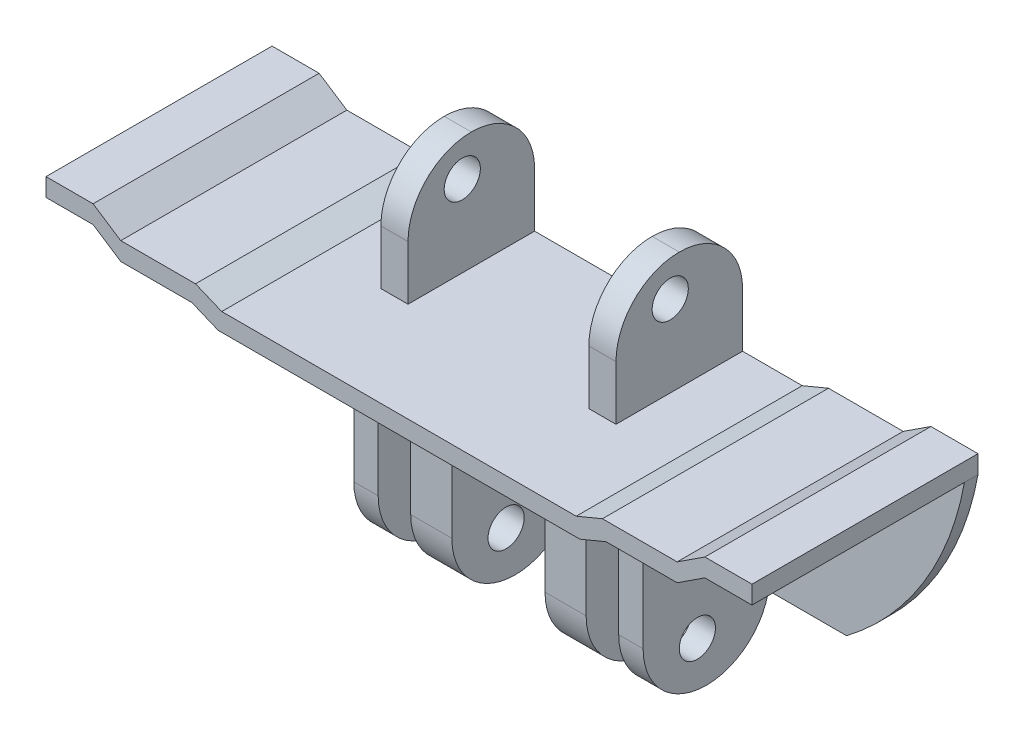
SolidWorks part; units mm, degrees
ref_plane "Front Plane" through (0, 0, 0) normal (0, 0, 1) x (1, 0, 0)
ref_plane "Top Plane" through (0, 0, 0) normal (0, 1, 0) x (1, 0, 0)
ref_plane "Right Plane" through (0, 0, 0) normal (1, 0, 0) x (0, 0, -1)
sketch "Sketch2" plane through (0, 0, 0) normal (0, 0, 1) x (1, 0, 0)
  line L0 (-5, 6) -> (-10, 6)
  line L1 (-5, 6) -> (5, 6) construction
  line L2 (-5, 6) -> (-5, -19) construction
  line L4 (5, 6) -> (5, -19) construction
  line L7 (-10, 6) -> (-10, -19)
  line L8 (-10, -19) -> (-5, -19)
  line L9 (-5, -19) -> (-5, 6)
  line L10 (0, 6) -> (0, -6) construction
  line L11 (10, -19) -> (5, -19)
  line L12 (10, 6) -> (10, -19)
  line L13 (5, 6) -> (10, 6)
  line L14 (5, -19) -> (5, 6)
  point P0 (0, 0)
  point P11 (0, 0)
  point P16 (0, 6)
  dimension "D1" = 25
  dimension "D2" = 10
  dimension "D3" = 5
extrude "Boss-Extrude1" add sketch "Sketch2" along normal blind 14
sketch "Sketch4" plane through (0, 0, 0) normal (0, 0, 1) x (1, 0, 0)
  line L0 (0, 0) -> (0, 50000) construction
  line L1 (-6.1796, 6) -> (49993.8204, 6) construction
  line L2 (-10, 6) -> (-20, 6)
  line L3 (10, 6) -> (20, 6)
  line L4 (-20, 6) -> (-22.9016, 7.2064)
  line L5 (-22.9016, 7.2064) -> (-26, 7.2064)
  line L6 (-10, 8) -> (-19.6008, 8)
  line L7 (-19.6008, 8) -> (-22.5024, 9.2064)
  line L8 (-22.5024, 9.2064) -> (-26, 9.2064)
  line L9 (-26, 9.2064) -> (-26, 7.2064)
  line L10 (-10, 6) -> (10, 6)
  line L11 (-10, 8) -> (10, 8)
  line L12 (10, 8) -> (19.6008, 8)
  line L13 (19.6008, 8) -> (22.5024, 9.2064)
  line L14 (20, 6) -> (22.9016, 7.2064)
  line L15 (22.9016, 7.2064) -> (26, 7.2064)
  line L17 (22.5024, 9.2064) -> (26, 9.2064)
  line L18 (-26, 7.2064) -> (-30.766, 7.2064)
  line L19 (-30.766, 7.2064) -> (-33.8312, 9.2064)
  line L20 (-33.8312, 9.2064) -> (-39.0379, 9.2064)
  line L21 (-39.0379, 9.2064) -> (-39.0379, 11.2064)
  line L22 (-39.0379, 11.2064) -> (-33.8312, 11.2064)
  line L23 (-26, 9.2064) -> (-30.766, 9.2064)
  line L24 (-30.766, 9.2064) -> (-33.8312, 11.2064)
  line L25 (26, 7.2064) -> (30.766, 7.2064)
  line L26 (26, 9.2064) -> (30.766, 9.2064)
  line L27 (30.766, 9.2064) -> (33.8312, 11.2064)
  line L28 (30.766, 7.2064) -> (33.8312, 9.2064)
  line L29 (33.8312, 9.2064) -> (39.0379, 9.2064)
  line L30 (39.0379, 9.2064) -> (39.0379, 11.2064)
  line L31 (39.0379, 11.2064) -> (33.8312, 11.2064)
  line L32 (26, 7.2064) -> (26, 9.2064)
  point P19 (0, 6)
  point P20 (0, 8)
  dimension "D1" = 10
  dimension "D2" = 2
extrude "Boss-Extrude3" add sketch "Sketch4" along normal blind 25 contours L23 L24 L22 L21 L20 L19 L18 L9 | L15 L32 L17 L13 L12 L11 L6 L7 L8 L9 L5 L4 L2 L10 L3 L14 | L32 L25 L28 L29 L30 L31 L27 L26 region at (0, 7.2239, 0) region at (-32.5189, 9.2402, 0) region at (32.5189, 9.2402, 0)
sketch "Sketch9" plane through (0, 0, 14) normal (0, 0, 1) x (1, 0, 0)
  line L0 (-10, -19) -> (-5, -19) construction
  line L1 (-5, 6) -> (-7.5, 6)
  line L2 (-5, 6) -> (-5, -19)
  line L3 (-5, -19) -> (-7.5, -19)
  line L4 (-7.5, 6) -> (-7.5, -19)
  line L5 (0, 7.972) -> (0, -7.972) construction
  line L6 (5, -19) -> (7.5, -19)
  line L7 (7.5, 6) -> (7.5, -19)
  line L8 (5, 6) -> (7.5, 6)
  line L9 (5, 6) -> (5, -19)
  point P11 (0, 0)
  dimension "D1" = 2.5
extrude "Cut-Extrude1" [suppressed] cut sketch "Sketch9" against normal blind 10
sketch "Sketch5" plane through (0, 0, 0) normal (0, 0, 1) x (1, 0, 0)
  line L0 (-10, 4.6) -> (-10, 50004.6) construction
  line L1 (0, 0) -> (0, 50000) construction
  line L2 (-10, 8) -> (-10, 21)
  line L3 (-19.6008, 8) -> (19.6008, 8) construction
  line L4 (-10, 21) -> (-13, 21)
  line L5 (-13, 21) -> (-13, 8)
  line L6 (-13, 8) -> (-10, 8)
  line L7 (13, 8) -> (10, 8)
  line L8 (13, 21) -> (13, 8)
  line L9 (10, 21) -> (13, 21)
  line L10 (10, 8) -> (10, 21)
  dimension "D1" = 3
  dimension "D2" = 13
extrude "Boss-Extrude4" add sketch "Sketch5" along normal blind 14
sketch "Sketch7" plane through (0, 0, 0) normal (0, 0, 1) x (1, 0, 0)
  line L0 (-13, 5.6) -> (-13, -49994.4) construction
  line L1 (-19.6008, 5.6) -> (-19.6008, -49994.4) construction
  line L2 (-10.0004, -19) -> (49989.9996, -19) construction
  line L3 (-15.0004, 6) -> (-50015.0004, 6) construction
  line L4 (-16, 6) -> (-16, -19)
  line L5 (-16, -19) -> (-13, -19)
  line L6 (-13, -19) -> (-13, 6)
  line L7 (-13, 6) -> (-16, 6)
  line L8 (0, 0) -> (0, -50000) construction
  line L13 (0, -13.75) -> (0, 13.75) construction
  line L14 (13, -19) -> (13, 6)
  line L15 (16, -19) -> (13, -19)
  line L16 (16, 6) -> (16, -19)
  line L17 (13, 6) -> (16, 6)
  dimension "D1" = 3
extrude "Boss-Extrude5" add sketch "Sketch7" along normal blind 14
sketch "Sketch15" plane through (0, -19, 0) normal (0, -1, 0) x (1, 0, 0)
  line L16 (-10, 14) -> (-9.7, 14)
  line L17 (-10, 14) -> (-5, 14) construction
  line L18 (-10, 14) -> (-10, 0) construction
  line L19 (-9.7, 14) -> (-9.7, 0)
  line L20 (-10, 0) -> (-5, 0) construction
  line L21 (-9.7, 0) -> (-10, 0)
  line L22 (-10, 0) -> (-10, 14)
  line L23 (0, -13.75) -> (0, 13.75) construction
  line L24 (9.7, 0) -> (10, 0)
  line L25 (9.7, 14) -> (9.7, 0)
  line L26 (10, 14) -> (9.7, 14)
  line L27 (10, 0) -> (10, 14)
  line L28 (-13, 14) -> (-13.3, 14)
  line L29 (-16, 14) -> (-13, 14) construction
  line L30 (-13.3, 14) -> (-13.3, 0)
  line L31 (-16, 0) -> (-13, 0) construction
  line L32 (-13.3, 0) -> (-13, 0)
  line L33 (-13, 0) -> (-13, 14)
  line L34 (13.3, 0) -> (13, 0)
  line L35 (13.3, 14) -> (13.3, 0)
  line L36 (13, 14) -> (13.3, 14)
  line L37 (13, 0) -> (13, 14)
  dimension "D1" = 0.3
  dimension "D2" = 0.3
extrude "Cut-Extrude2" cut sketch "Sketch15" against normal up to surface (25 mm away) up to face at (0, 6, 8.1)
sketch "Sketch16" plane through (0, -19, 0) normal (0, -1, 0) x (1, 0, 0)
  line L0 (-5, 14) -> (-5.15, 14)
  line L1 (-9.7, 14) -> (-5, 14) construction
  line L2 (-5.15, 14) -> (-5.15, 0)
  line L3 (-9.7, 0) -> (-5, 0) construction
  line L4 (-5.15, 0) -> (-5, 0)
  line L5 (-5, 0) -> (-5, 14)
  line L6 (0, -13.75) -> (0, 13.75) construction
  line L7 (5.15, 0) -> (5, 0)
  line L8 (5.15, 14) -> (5.15, 0)
  line L9 (5, 14) -> (5.15, 14)
  line L10 (5, 0) -> (5, 14)
  dimension "D1" = 0.15
extrude "Cut-Extrude3" cut sketch "Sketch16" against normal up to surface (25 mm away) up to face at (0, 6, 8.1)
fillet "Fillet1" radius 7 8 edges at (7.425, -19, 0) (7.425, -19, 14) (-7.425, -19, 0) (-7.425, -19, 14) (-14.65, -19, 0) (-14.65, -19, 14) (14.65, -19, 0) (14.65, -19, 14)
hole_wizard "Ø4.0mm Dowel Hole2" positions "Sketch10" profile "Sketch11" hole size "Ø4.0" standard "ANSI Metric" end condition through all
sketch "Sketch10" plane through (16, 0, 0) normal (1, 0, 0) x (0, 0, -1)
  line L7 (-25, 6) -> (0, 6) construction
  line L9 (-14, -12) -> (-14, 6) construction
  point P0 (-8, -14)
  dimension "D1" = 6
  dimension "D2" = 20
sketch "Sketch11" plane through (16, -14, 8) normal (0, 1, 0) x (0, 0, -1)
  line L0 (0, 0) -> (0, 55.0379)
  line L1 (0, 55.0379) -> (2, 55.0379)
  line L2 (2, 55.0379) -> (2, 0)
  line L5 (2, 0) -> (0, 0)
  line L11 (0, -6.35) -> (0, 107.95) construction
  dimension "Thru Hole Dia." = 4
  dimension "Thru Hole Depth" = 55.0379
fillet "Fillet2" radius 7 4 edges at (-11.5, 21, 0) (-11.5, 21, 14) (11.5, 21, 0) (11.5, 21, 14)
hole_wizard "Ø4.0mm Dowel Hole1" positions "Sketch12" profile "Sketch13" hole size "Ø4.0" standard "ANSI Metric"
sketch "Sketch12" plane through (13, 0, 0) normal (1, 0, 0) x (0, 0, -1)
  line L1 (-25, 8) -> (0, 8) construction
  line L2 (-25, 8) -> (0, 8)
  circle A8 centre (-8, -14) radius 2 construction
  circle A9 centre (-8, -14) radius 2
  point P10 (-8, 17)
  dimension "D1" = 9
sketch "Sketch13" plane through (13, 17, 8) normal (0, 1, 0) x (0, 0, -1)
  line L0 (0, 0) -> (0, 27.2017)
  line L1 (0, 27.2017) -> (2, 26)
  line L2 (2, 26) -> (2, 0)
  line L5 (2, 0) -> (0, 0)
  line L10 (0, 27.2017) -> (-2, 26) construction
  line L11 (0, -6.35) -> (0, 107.95) construction
  dimension "Hole Dia." = 4
  dimension "Hole Depth" = 26
  dimension "Drill Angle" = 118
sketch "Sketch14" plane through (0, 0, 0) normal (0, 0, 1) x (1, 0, 0)
  line L4 (0, 14.6739) -> (0, -14.6739) construction
  line L5 (-26, 7.2064) -> (-22.9016, 7.2064)
  line L6 (-26, 6) -> (-26, 7.2064)
  line L7 (-20, 6) -> (-26, 6)
  line L8 (-22.9016, 7.2064) -> (-20, 6)
  line L13 (-16, 6) -> (-20, 6)
  line L14 (-26, -12) -> (-26, 6)
  line L15 (-16, -12) -> (-26, -12)
  line L18 (-16, 6) -> (-16, -12)
  line L21 (16, 6) -> (16, -12)
  line L22 (16, -12) -> (26, -12)
  line L23 (26, -12) -> (26, 6)
  line L24 (16, 6) -> (20, 6)
  line L25 (22.9016, 7.2064) -> (20, 6)
  line L26 (20, 6) -> (26, 6)
  line L27 (26, 6) -> (26, 7.2064)
  line L28 (26, 7.2064) -> (22.9016, 7.2064)
  line L29 (33.8312, 9.2064) -> (39.0379, 9.2064) construction
  line L30 (30.766, 7.2064) -> (33.8312, 9.2064) construction
  line L31 (22.9016, 7.2064) -> (30.766, 7.2064) construction
  line L32 (33.8312, 9.2064) -> (39.0379, 9.2064)
  line L33 (30.766, 7.2064) -> (33.8312, 9.2064)
  line L34 (22.9016, 7.2064) -> (30.766, 7.2064)
  line L35 (-33.8312, 9.2064) -> (-39.0379, 9.2064) construction
  line L36 (-30.766, 7.2064) -> (-33.8312, 9.2064) construction
  line L37 (-22.9016, 7.2064) -> (-30.766, 7.2064) construction
  line L38 (-33.8312, 9.2064) -> (-39.0379, 9.2064)
  line L39 (-30.766, 7.2064) -> (-33.8312, 9.2064)
  line L40 (-22.9016, 7.2064) -> (-30.766, 7.2064)
  line L41 (-13.3, -12) -> (-16, -12) construction
  arc A0 (-39.0379, 9.2064) -> (-26, -12) centre (-5.4018, 15.2751) ccw
  arc A1 (26, -12) -> (39.0379, 9.2064) centre (5.4018, 15.2751) ccw
  point P11 (0, 0)
extrude "Boss-Extrude6" add sketch "Sketch14" along normal blind 1.5 contours L8 L5 L6 L7 | L14 L13 L7 | L27 L28 L25 L26 | L26 L24 L21 L22 L23 | L38 A0 L14 L6 L40 L39 | L23 A1 L32 L33 L34 L27 region at (-23.6483, 6.5391, 0) region at (-31.1404, 0.7095, 0) region at (-21, -3, 0) region at (21, -3, 0) region at (23.6483, 6.5391, 0) region at (31.1404, 0.7095, 0)
sketch "Sketch18" plane through (-5.15, 0, 0) normal (1, 0, 0) x (0, 0, -1)
  line L10 (-7.9408, -17.3481) -> (-22.2123, -17.3481)
  line L17 (-5.13, -12.2747) -> (-8.0592, -10.6519)
  line L18 (-8.0592, -10.6519) -> (-10.9291, -12.3772)
  line L19 (-10.9291, -12.3772) -> (-10.87, -15.7253)
  line L20 (-10.87, -15.7253) -> (-7.9408, -17.3481)
  line L21 (-7.9408, -17.3481) -> (-5.0709, -15.6228)
  line L22 (-5.0709, -15.6228) -> (-5.13, -12.2747)
  line L23 (-8.0592, -10.6519) -> (-22.2123, -10.902)
  line L24 (-22.2123, -10.902) -> (-22.2123, -17.3481)
  circle A0 centre (-8, -14) radius 2.9 construction
  circle M7 centre (-8, -14) radius 2
  arc M8 (-14, -12) -> (-7, -19) centre (-7, -12) ccw
  line M12 (-14, 6) -> (-14, -12)
  dimension "D1" = 5.8
extrude "Cut-Extrude4" [suppressed] cut sketch "Sketch18" against normal blind 2.8 contours L21 L22 L17 L18 L19 L20 M7 | L23 L24 L10 M8 M12 | L18 L23 L10 L20 L19 M12 M8
mirror "Mirror1" [suppressed] about plane through (0, 0, 0) normal (1, 0, 0)
